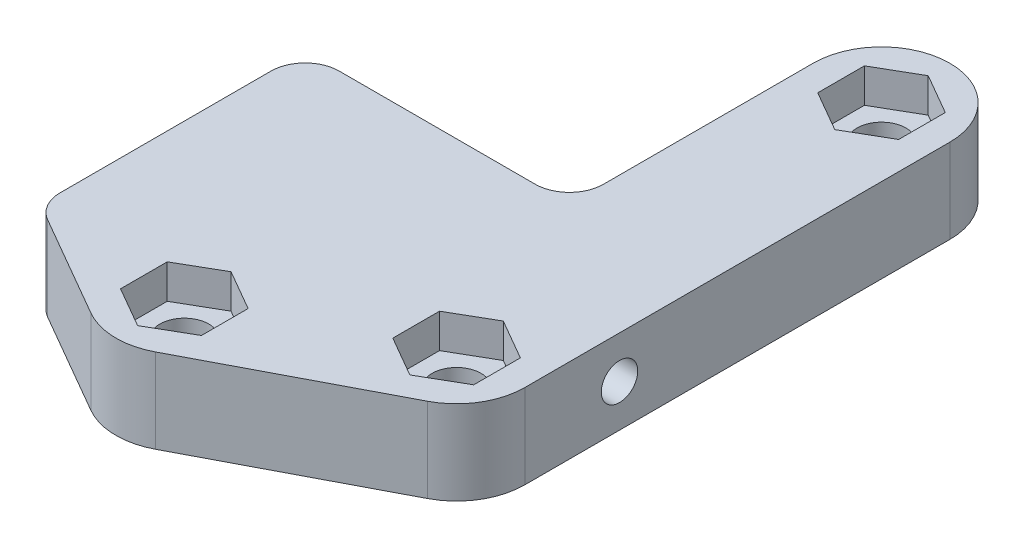
SolidWorks part; units mm, degrees
ref_plane "Front Plane" through (0, 0, 0) normal (0, 0, 1) x (1, 0, 0)
ref_plane "Top Plane" through (0, 0, 0) normal (0, 1, 0) x (1, 0, 0)
ref_plane "Right Plane" through (0, 0, 0) normal (1, 0, 0) x (0, 0, -1)
sketch "Sketch2" plane through (0, 0, 0) normal (0, 1, 0) x (1, 0, 0)
  line L0 (-11.5, -22.6506) -> (11.5, -22.6506) construction
  line L1 (0, -22.6506) -> (0, 22.6506) construction
  line L2 (-11.5, -22.6506) -> (-11.5, 22.6506) construction
  line L3 (-11.5, 22.6506) -> (11.5, 22.6506) construction
  line L4 (-13.5, -25.9846) -> (-3, -32.0468)
  line L5 (2.7777, -32.1689) -> (18.4777, -23.9689)
  line L6 (21.7, -18.6506) -> (21.7, 18.6506)
  line L7 (1.8518, -30.3962) -> (17.5518, -22.1962) construction
  line L8 (11.5, -22.6506) -> (11.5, 22.6506) construction
  line L9 (11.5, 22.6506) -> (15.7, 22.6506) construction
  line L10 (19.7, -18.6506) -> (19.7, 18.6506) construction
  line L11 (-11.5, -22.6506) -> (-11.5, -24.8299) construction
  line L12 (-11.5, -24.8299) -> (-2, -30.3147) construction
  line L13 (0, -26.8506) -> (0, -22.6506) construction
  line L14 (15.7, -18.6506) -> (11.5, -18.6506) construction
  line L15 (11.5, 0) -> (19.7, 0) construction
  line L16 (11.5, 24.6506) -> (15.7, 24.6506)
  line L17 (-13.5, 24.6506) -> (11.5, 24.6506)
  line L18 (-13.5, -22.6506) -> (-13.5, 24.6506)
  line L19 (-13.5, -22.6506) -> (-13.5, -25.9846)
  arc A0 (-2, -30.3147) -> (1.8518, -30.3962) centre (0, -26.8506) ccw construction
  circle A1 centre (0, -26.8506) radius 2.15
  arc A2 (17.5518, -22.1962) -> (19.7, -18.6506) centre (15.7, -18.6506) ccw construction
  arc A3 (15.7, 22.6506) -> (19.7, 18.6506) centre (15.7, 18.6506) cw construction
  circle A4 centre (15.7, -18.6506) radius 2.15
  circle A5 centre (15.7, 18.6506) radius 2.15
  arc A6 (-3, -32.0468) -> (2.7777, -32.1689) centre (0, -26.8506) ccw
  arc A7 (18.4777, -23.9689) -> (21.7, -18.6506) centre (15.7, -18.6506) ccw
  arc A8 (15.7, 24.6506) -> (21.7, 18.6506) centre (15.7, 18.6506) cw
  point P3 (0, 0)
  dimension "D3" = 4
  dimension "D4" = 4.3
  dimension "D1" = 45.3013
  dimension "D2" = 23
  dimension "D5" = 2.1793
  dimension "D6" = 4.2
  dimension "D7" = 2
extrude "Boss-Extrude1" add sketch "Sketch2" along normal blind 7.4
sketch "Sketch3" plane through (21.7, 0, 0) normal (-1, 0, 0) x (0, 0, 1)
  line L0 (10.3494, 7.4) -> (10.3494, 0) construction
  line L2 (-24.6506, 7.4) -> (25.9846, 7.4) construction
  line L5 (-24.6506, 0) -> (25.9846, 0) construction
  line L6 (-24.6506, 7.4) -> (-24.6506, 0) construction
  circle A0 centre (10.3494, 3.7) radius 1.6
  point P8 (0, 0)
  point P9 (10.3494, 3.7)
  dimension "D1" = 3.2
  dimension "D2" = 35
extrude "Cut-Extrude4" cut sketch "Sketch3" against normal through all and the other way through all
sketch "Sketch4" plane through (0, 7.4, 0) normal (0, -1, 0) x (1, 0, 0)
  line L1 (0, 22.7514) -> (3.55, 24.801)
  line L2 (3.55, 24.801) -> (3.55, 28.9002)
  line L3 (3.55, 28.9002) -> (0, 30.9498)
  line L4 (0, 30.9498) -> (-3.55, 28.9002)
  line L5 (-3.55, 28.9002) -> (-3.55, 24.801)
  line L6 (-3.55, 24.801) -> (0, 22.7514)
  line L7 (15.7, 14.5514) -> (19.25, 16.601)
  line L8 (19.25, 16.601) -> (19.25, 20.7002)
  line L9 (19.25, 20.7002) -> (15.7, 22.7498)
  line L10 (15.7, 22.7498) -> (12.15, 20.7002)
  line L11 (12.15, 20.7002) -> (12.15, 16.601)
  line L12 (12.15, 16.601) -> (15.7, 14.5514)
  line L13 (12.15, -20.7002) -> (15.7, -22.7498)
  line L14 (15.7, -22.7498) -> (19.25, -20.7002)
  line L15 (19.25, -20.7002) -> (19.25, -16.601)
  line L16 (19.25, -16.601) -> (15.7, -14.5514)
  line L17 (15.7, -14.5514) -> (12.15, -16.601)
  line L18 (12.15, -16.601) -> (12.15, -20.7002)
  circle A0 centre (0, 26.8506) radius 3.55 construction
  circle A1 centre (15.7, 18.6506) radius 3.55 construction
  circle A2 centre (15.7, -18.6506) radius 3.55 construction
  point P19 (3.4943, 25.0992)
  dimension "D1" = 7.1
extrude "Cut-Extrude1" cut sketch "Sketch4" along normal blind 3
sketch "Sketch5" plane through (0, 7.4, 0) normal (0, 1, 0) x (1, 0, 0)
  line L0 (-13.5, -8.7494) -> (-13.5, -11.9494) construction
  line L1 (-13.5, -8.7494) -> (-13.5, -11.9494) construction
  line L2 (-13.5, 24.6506) -> (-13.5, -2.7494)
  line L3 (-13.5, 24.6506) -> (-13.5, -25.9846) construction
  line L4 (-13.5, 24.6506) -> (15.7, 24.6506)
  line L5 (15.7, 24.6506) -> (-13.5, 24.6506) construction
  line L7 (21.7, -18.6506) -> (21.7, 18.6506) construction
  line L8 (-13.5, -8.7494) -> (21.7, -8.7494) construction
  line L9 (-13.5, -8.7494) -> (-13.5, -11.9494) construction
  line L10 (-13.5, -11.9494) -> (21.7, -11.9494) construction
  line L11 (21.7, -8.7494) -> (21.7, -11.9494) construction
  line L12 (9.7, 18.6506) -> (9.7, -2.7494)
  line L13 (9.7, -2.7494) -> (-13.5, -2.7494)
  arc A0 (15.7, 24.6506) -> (9.7, 18.6506) centre (15.7, 18.6506) ccw
  point P13 (-13.0137, 24.6506)
  line M9 (-13.5, 24.6506) -> (-13.5, -25.9846)
  line M16 (15.7, 24.6506) -> (-13.5, 24.6506)
  dimension "D1" = 6
extrude "Cut-Extrude5" cut sketch "Sketch5" against normal through all contours M9 M16 region at (-1.7446, 7.4, -11.099)
fillet "Fillet1" radius 3 3 edges at (-13.5, 3.7, 25.9846) (9.7, 3.7, 2.7494) (-13.5, 3.7, 2.7494)
